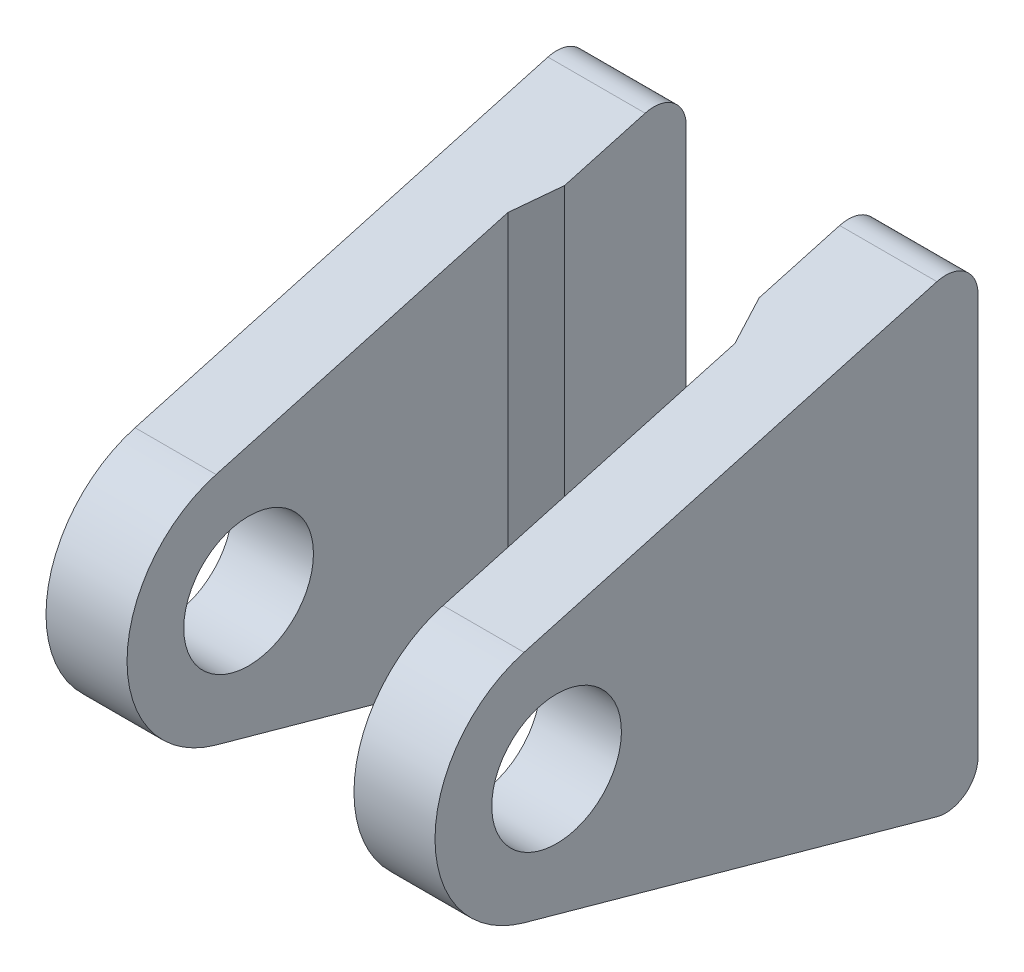
SolidWorks part; units mm, degrees
ref_plane "前视基准面" through (0, 0, 0) normal (0, 0, 1) x (1, 0, 0)
ref_plane "上视基准面" through (0, 0, 0) normal (0, 1, 0) x (1, 0, 0)
ref_plane "右视基准面" through (0, 0, 0) normal (1, 0, 0) x (0, 0, -1)
sketch "草图1" plane through (0, 0, 0) normal (0, 0, 1) x (1, 0, 0)
  line L1 (-12, 15) -> (12, 15)
  line L2 (-12, 15) -> (-12, -15)
  line L3 (-12, -15) -> (12, -15)
  line L4 (12, 15) -> (12, -15)
  line L5 (-12, 15) -> (12, -15) construction
  line L6 (-12, -15) -> (12, 15) construction
  point P0 (0, 0)
  point P6 (0, 0)
  dimension "D1" = 24
  dimension "D2" = 30
extrude "凸台-拉伸1" add sketch "草图1" along normal blind 4
sketch "草图4" plane through (-12, 0, 0) normal (-1, 0, 0) x (0, 0, 1)
  line L0 (4, 15) -> (32.0058, 7.2268)
  line L1 (4, -15) -> (32.0058, -7.2268)
  line L2 (4, 15) -> (4, -15)
  arc A0 (32.0058, -7.2268) -> (32.0058, 7.2268) centre (30, 0) ccw
  dimension "D2" = 15
  dimension "D1" = 30
extrude "凸台-拉伸2" add sketch "草图4" against normal blind 5
extrude "凸台-拉伸3" add sketch "草图4<2>" along normal blind 5 from surface starting at face at (12, 0, 2)
sketch "草图4<2>" plane through (-12, 0, 0) normal (-1, 0, 0) x (0, 0, 1) same geometry as "草图4"
sketch "草图9" plane through (0, 0, 0) normal (0, 0, -1) x (-1, 0, 0)
  line L1 (-9, 8) -> (9, 8)
  line L2 (-9, 8) -> (-9, -8)
  line L3 (-9, -8) -> (9, -8)
  line L4 (9, 8) -> (9, -8)
  line L5 (-9, 8) -> (9, -8) construction
  line L6 (-9, -8) -> (9, 8) construction
  point P0 (0, 0)
  dimension "D1" = 18
  dimension "D2" = 16
hole_wizard "M6 螺纹孔1" positions "3D草图1" profile "草图12" tap size "M6" standard "ISO" end condition up to next
sketch3d "3D草图1"
  point P0 (-12, 0, 30)
sketch "草图12" plane through (-12, 0, 30) normal (0, 1, 0) x (0, 0, 1)
  line L0 (0, 0) -> (0, 5)
  line L1 (0, 5) -> (2.5, 5)
  line L2 (2.5, 5) -> (2.5, 0)
  line L5 (2.5, 0) -> (0, 0)
  line L11 (0, -6.35) -> (0, 107.95) construction
  dimension "通孔螺纹孔钻头直径" = 5
  dimension "通孔螺纹孔钻头深度" = 5
cosmetic thread "孔螺蚊线5" parameters "D2"=6
sketch "草图13" plane through (12, 0, 0) normal (1, 0, 0) x (0, 0, -1)
  circle A0 centre (-30, 0) radius 4
  dimension "D1" = 8
extrude "切除-拉伸1" cut sketch "草图13" against normal through all
chamfer "倒角1" distance 4 distance2 10 1 edges at (7, 0, 4) first distance on face at (0, 0, 4)
sketch "草图14" plane through (0, 0, 4) normal (0, 0, 1) x (1, 0, 0)
  line L1 (-7, 15) -> (3, 15)
  line L2 (-7, 15) -> (-7, -15)
  line L3 (-7, -15) -> (3, -15)
  line L4 (3, 15) -> (3, -15)
chamfer "倒角2" distance 10 distance2 4 1 edges at (-7, 0, 4) first distance on face at (-7, -4, 30)
hole_wizard "M5 螺纹孔1" positions "草图10" profile "草图11" tap size "M5" standard "ISO"
sketch "草图10" plane through (0, 0, 0) normal (0, 0, -1) x (-1, 0, 0)
  point P0 (-9, 8)
  point P3 (9, 8)
  point P6 (9, -8)
  point P9 (-9, -8)
cosmetic thread "孔螺蚊线6" parameters "D1"=10, "D2"=5
cosmetic thread "孔螺蚊线7" parameters "D1"=10, "D2"=5
cosmetic thread "孔螺蚊线8" parameters "D1"=10, "D2"=5
cosmetic thread "孔螺蚊线9" parameters "D1"=10, "D2"=5
sketch "草图11" plane through (9, 8, 0) normal (1, 0, 0) x (0, 1, 0)
  line L0 (0, 0) -> (0, 11.2618)
  line L1 (0, 11.2618) -> (2.1, 10)
  line L2 (2.1, 10) -> (2.1, 0)
  line L5 (2.1, 0) -> (0, 0)
  line L10 (0, 11.2618) -> (-2.1, 10) construction
  line L11 (0, -6.35) -> (0, 107.95) construction
  dimension "螺纹孔钻头直径" = 4.2
  dimension "螺纹孔钻头深度" = 10
  dimension "导头角度" = 118
sketch "草图15" plane through (0, 0, 0) normal (0, 0, -1) x (-1, 0, 0)
  line L0 (7, -15) -> (-3, -15) construction
  line L1 (-6, 15) -> (6, 15)
  line L2 (-6, 15) -> (-6, -15)
  line L3 (-6, -15) -> (6, -15)
  line L4 (6, 15) -> (6, -15)
  line L5 (-6, 15) -> (6, -15) construction
  line L6 (-6, -15) -> (6, 15) construction
  point P0 (0, 0)
  dimension "D1" = 12
extrude "切除-拉伸2" cut sketch "草图15" against normal through all
sketch "草图16" plane through (0, 0, 0) normal (0, 0, -1) x (-1, 0, 0)
  line L0 (12, 15) -> (12, -15) construction
  line L1 (-12, 15) -> (12, 15)
  line L2 (-12, 15) -> (-12, -15)
  line L3 (-12, -15) -> (12, -15)
  line L4 (12, 15) -> (12, -15)
  line L5 (-12, 15) -> (12, -15) construction
  line L6 (-12, -15) -> (12, 15) construction
  point P0 (0, 0)
extrude "切除-拉伸3" cut sketch "草图16" against normal blind 4
fillet "圆角1" radius 2 2 edges at (-9, 15, 4) (-9, -15, 4)
fillet "圆角2" radius 2 2 edges at (9, 15, 4) (9, -15, 4)
